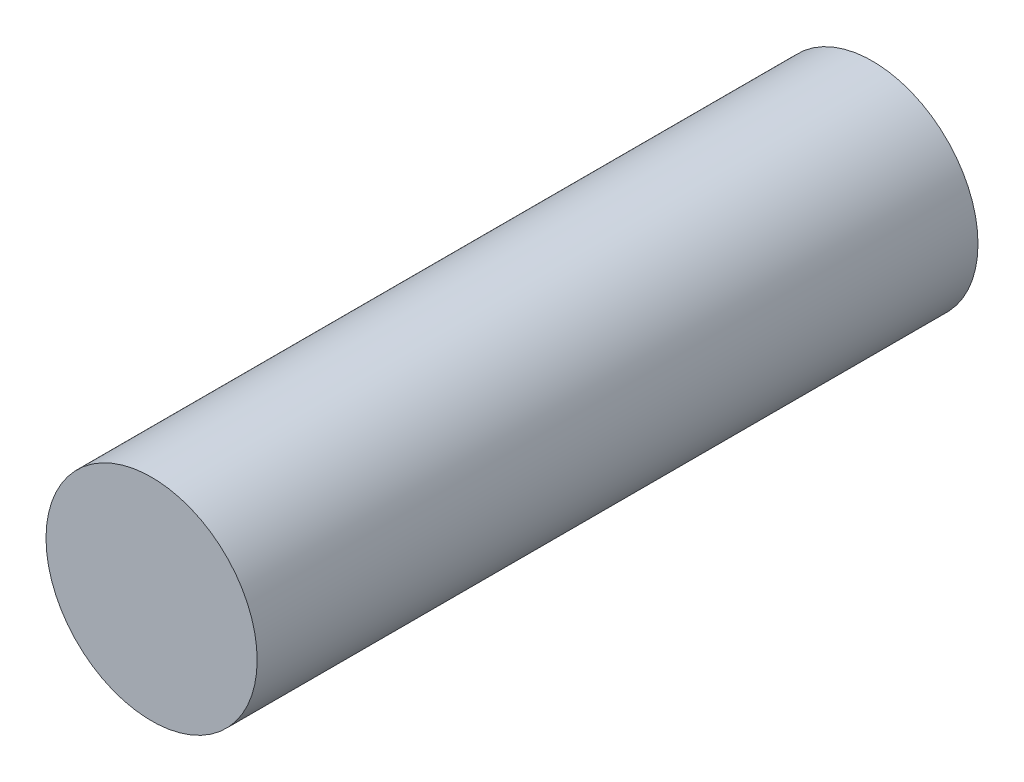
SolidWorks part; units mm, degrees
ref_plane "Front Plane" through (0, 0, 0) normal (0, 0, 1) x (1, 0, 0)
ref_plane "Top Plane" through (0, 0, 0) normal (0, 1, 0) x (1, 0, 0)
ref_plane "Right Plane" through (0, 0, 0) normal (1, 0, 0) x (0, 0, -1)
sketch "Sketch1" plane through (0, 0, 0) normal (0, 0, 1) x (1, 0, 0)
  circle A0 centre (0, 0) radius 2.49
  dimension "D1" = 4.98
extrude "Boss-Extrude1" add sketch "Sketch1" along normal mid plane 17
sketch "Sketch2" plane through (0, 0, 0) normal (0, 0, 1) x (1, 0, 0)
  circle A0 centre (0, 0) radius 2.5 construction
  dimension "D1" = 5
